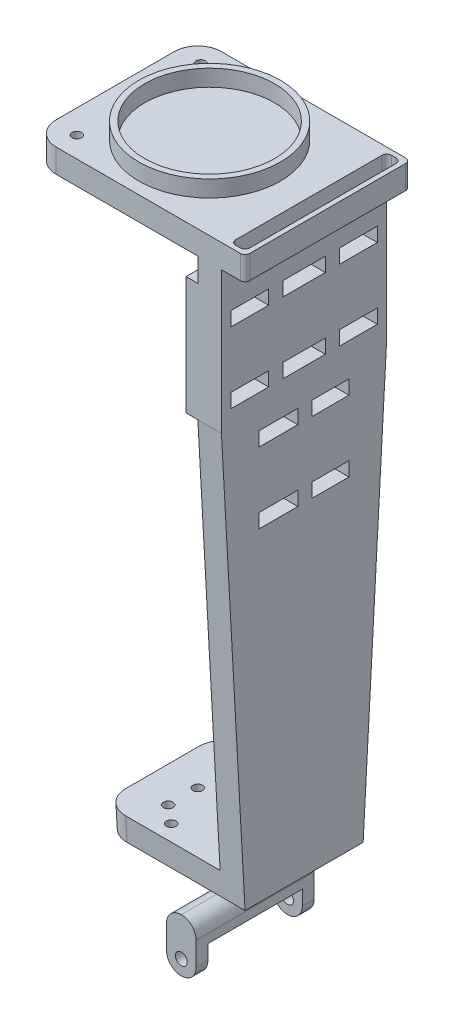
SolidWorks part; units mm, degrees
ref_plane "Front Plane" through (0, 0, 0) normal (0, 0, 1) x (1, 0, 0)
ref_plane "Top Plane" through (0, 0, 0) normal (0, 1, 0) x (1, 0, 0)
ref_plane "Right Plane" through (0, 0, 0) normal (1, 0, 0) x (0, 0, -1)
sketch "Sketch1" plane through (0, 0, 0) normal (0, 1, 0) x (1, 0, 0)
  line L1 (0, 0) -> (-80, 0)
  line L2 (0, 0) -> (0, -70)
  line L3 (0, -70) -> (-80, -70)
  line L4 (-80, 0) -> (-80, -70)
  dimension "D1" = 80
  dimension "D2" = 70
extrude "Boss-Extrude1" add sketch "Sketch1" along normal blind 10
sketch "Sketch2" plane through (0, 0, 0) normal (0, -1, 0) x (1, 0, 0)
  line L0 (0, 0) -> (-80, 0) construction
  line L1 (0, 70) -> (-10, 70)
  line L2 (0, 70) -> (0, 0)
  line L3 (0, 0) -> (-10, 0)
  line L4 (-10, 70) -> (-10, 0)
  dimension "D1" = 10
extrude "Boss-Extrude2" add sketch "Sketch2" along normal blind 450
sketch "Sketch3" plane through (0, 10, 0) normal (0, 1, 0) x (1, 0, 0)
  line L0 (0, 0) -> (-80, -70) construction
  line L1 (-80, -70) -> (-80, 0) construction
  line L2 (-80, 0) -> (0, -70) construction
  line L3 (0, -70) -> (0, 0) construction
  line L4 (0, 0) -> (-80, 0) construction
  line L5 (-80, 0) -> (-80, -70) construction
  line L6 (-80, -70) -> (0, -70) construction
  circle A0 centre (-40, -35) radius 27.5
  circle A1 centre (-40, -35) radius 30
  dimension "D1" = 55
  dimension "D2" = 60
extrude "Boss-Extrude3" add sketch "Sketch3" along normal blind 7
sketch "Sketch6" plane through (0, 10, 0) normal (0, 1, 0) x (1, 0, 0)
  line L0 (-80, -70) -> (-80, -35) construction
  line L1 (-80, 0) -> (-80, -70) construction
  line L2 (-80, -35) -> (-40, -70) construction
  line L3 (-80, -70) -> (0, -70) construction
  line L4 (-40, -70) -> (-80, -70) construction
  line L5 (-80, -70) -> (-80, -35) construction
  line L6 (-80, -35) -> (-80, 0) construction
  line L7 (-80, 0) -> (-40, 0) construction
  line L8 (0, 0) -> (-80, 0) construction
  line L9 (-40, 0) -> (-80, -35) construction
  line L10 (-80, -52.5) -> (-60, -70) construction
  line L11 (-80, -17.5) -> (-60, 0) construction
  circle A0 centre (-70, -61.25) radius 2
  circle A1 centre (-70, -8.75) radius 2
  dimension "D1" = 4
  dimension "D2" = 4
extrude "Cut-Extrude3" cut sketch "Sketch6" against normal blind 27
sketch "Sketch7" plane through (-10, 0, 0) normal (-1, 0, 0) x (0, 0, 1)
  line L0 (70, -450) -> (70, 0) construction
  line L1 (0, -450) -> (70, -450)
  line L2 (0, -450) -> (0, -240)
  line L3 (0, -240) -> (70, -240)
  line L4 (70, -450) -> (70, -240)
  dimension "D1" = 210
extrude "Cut-Extrude4" cut sketch "Sketch7" against normal blind 27
sketch "Sketch10" plane through (-10, 0, 0) normal (-1, 0, 0) x (0, 0, 1)
  line L0 (0, 0) -> (0, -120) construction
  line L1 (0, -240) -> (0, 0) construction
  line L2 (0, -120) -> (70, -120) construction
  line L3 (70, -240) -> (70, 0) construction
  line L4 (70, -120) -> (70, 0) construction
  line L5 (70, 0) -> (0, 0) construction
  line L6 (0, 0) -> (70, -120) construction
  line L7 (70, 0) -> (0, -120) construction
  line L8 (0, -240) -> (70, -240) construction
  line L9 (70, -240) -> (35, -240) construction
  line L10 (35, -240) -> (0, -240) construction
  line L11 (0, -60) -> (10, -240)
  line L12 (0, -240) -> (0, -60)
  line L13 (70, -60) -> (60, -240)
  line L14 (60, -240) -> (70, -240)
  line L15 (70, -240) -> (70, -60)
  line L16 (0, -240) -> (10, -240)
  dimension "D1" = 10
  dimension "D2" = 10
extrude "Cut-Extrude5" cut sketch "Sketch10" against normal blind 70
sketch "Sketch11" plane through (-10, 0, 0) normal (-1, 0, 0) x (0, 0, 1)
  line L0 (10.1166, -240) -> (60, -240)
  line L1 (60, -240) -> (10, -240) construction
  line L2 (60, -240) -> (60.5556, -230)
  line L3 (70, -60) -> (60, -240) construction
  line L4 (60.5556, -230) -> (9.4444, -230)
  line L5 (10, -240) -> (0, -60) construction
  line L6 (9.4444, -230) -> (10.1166, -240)
  dimension "D1" = 10
extrude "Boss-Extrude5" add sketch "Sketch11" along normal blind 50
sketch "Sketch12" plane through (0, -240, 0) normal (0, -1, 0) x (1, 0, 0)
  line L0 (-60, 60) -> (0, 10) construction
  line L1 (0, 10) -> (0, 60) construction
  line L2 (0, 60) -> (-60, 10.1166) construction
  circle A0 centre (-30, 35) radius 7.5
  circle A1 centre (-30, 35) radius 10
  circle A2 centre (-30, 35) radius 2.5
  dimension "D1" = 15
  dimension "D2" = 20
  dimension "D3" = 5
extrude "Boss-Extrude6" add sketch "Sketch12" along normal blind 25 contours A2 | A1 A0 region at (-39.7172, -240, 35) region at (-30, -240, 35)
sketch "Sketch13" plane through (0, -240, 0) normal (0, -1, 0) x (-1, 0, 0)
  line L0 (60, -60) -> (0, -60) construction
  line L1 (0, -60) -> (0, -10) construction
  line L2 (0, -10) -> (60, -10.1166) construction
  line L3 (60, -10.1166) -> (60, -60) construction
  line L4 (60, -60) -> (30, -60) construction
  line L5 (30, -60) -> (0, -60) construction
  line L6 (0, -60) -> (0, -35) construction
  line L7 (0, -35) -> (0, -10) construction
  line L8 (0, -10) -> (30, -10.0583) construction
  line L9 (30, -10.0583) -> (60, -10.1166) construction
  line L10 (60, -10.1166) -> (60, -35.0583) construction
  line L11 (60, -35.0583) -> (60, -60) construction
  line L12 (60, -35.0583) -> (30, -60) construction
  line L13 (30, -60) -> (0, -35) construction
  line L14 (0, -35) -> (30, -10.0583) construction
  line L15 (30, -10.0583) -> (60, -35.0583) construction
  line L16 (45, -47.5291) -> (45, -60) construction
  line L17 (45, -60) -> (45, -10.0874) construction
  line L18 (45, -47.5291) -> (15, -47.5) construction
  line L19 (15, -47.5) -> (15, -22.5291) construction
  line L20 (15, -22.5291) -> (45, -22.5583) construction
  line L21 (45, -47.5291) -> (30, -60) construction
  line L22 (30, -60) -> (45, -47.5291) construction
  line L23 (45, -47.5291) -> (37.5, -53.7646) construction
  line L24 (37.5, -53.7646) -> (37.5, -16.3083) construction
  circle A0 centre (45, -47.5291) radius 2
  circle A1 centre (45, -22.5583) radius 2
  circle A2 centre (45, -35.0437) radius 2
  circle A3 centre (37.5, -53.7646) radius 2
  circle A4 centre (37.5, -16.3083) radius 2
  dimension "D1" = 4
  dimension "D2" = 4
  dimension "D3" = 4
  dimension "D4" = 4
  dimension "D5" = 4
extrude "Cut-Extrude6" cut sketch "Sketch13" against normal blind 25
sketch "Sketch14" plane through (-10, 0, 0) normal (-1, 0, 0) x (0, 0, 1)
  line L1 (0, -60) -> (24, -60)
  line L2 (0, -60) -> (0, -10)
  line L3 (0, -10) -> (24, -10)
  line L4 (24, -60) -> (24, -10)
  line L5 (2, -12) -> (22, -12)
  line L6 (2, -12) -> (2, -58)
  line L7 (2, -58) -> (22, -58)
  line L8 (22, -12) -> (22, -58)
  dimension "D1" = 50
  dimension "D2" = 24
  dimension "D3" = 2
  dimension "D4" = 2
  dimension "D5" = 2
  dimension "D6" = 2
extrude "Boss-Extrude7" add sketch "Sketch14" along normal blind 5
sketch "Sketch15" plane through (-10, 0, 0) normal (-1, 0, 0) x (0, 0, 1)
  line L1 (70, -60) -> (46, -60)
  line L2 (70, -60) -> (70, -10)
  line L3 (70, -10) -> (46, -10)
  line L4 (46, -60) -> (46, -10)
  line L5 (68, -58) -> (48, -58)
  line L6 (68, -58) -> (68, -12)
  line L7 (68, -12) -> (48, -12)
  line L8 (48, -58) -> (48, -12)
  dimension "D1" = 50
  dimension "D2" = 24
  dimension "D3" = 2
  dimension "D4" = 2
  dimension "D5" = 2
  dimension "D6" = 2
extrude "Boss-Extrude8" add sketch "Sketch15" along normal blind 5
sketch "Sketch16" plane through (-10, 0, 0) normal (-1, 0, 0) x (0, 0, 1)
  line L1 (24, -10) -> (46, -10)
  line L2 (24, -10) -> (24, -60)
  line L3 (24, -60) -> (46, -60)
  line L4 (46, -10) -> (46, -60)
  line L5 (24, -12) -> (46, -12)
  line L6 (24, -12) -> (24, -58)
  line L7 (24, -58) -> (46, -58)
  line L8 (46, -12) -> (46, -58)
  line M6 (24, -10) -> (24, -60)
  line M12 (46, -60) -> (46, -10)
  dimension "D1" = 2
  dimension "D2" = 2
extrude "Boss-Extrude9" add sketch "Sketch16" along normal blind 5 contours L5 L4 L1 M6 | L7 L3 M6 M12 region at (-10, -11, 35) region at (-10, -59, 35)
sketch "Sketch17" plane through (-10, 0, 0) normal (-1, 0, 0) x (0, 0, 1)
  line L0 (0, -60) -> (70, -60) construction
  line L1 (70, -60) -> (35, -60) construction
  line L2 (35, -60) -> (0, -60) construction
  line L3 (12, -12) -> (12, -60) construction
  line L4 (22, -12) -> (2, -12) construction
  line L5 (58, -12) -> (58, -60) construction
  line L6 (68, -12) -> (48, -12) construction
  line L7 (12, -60) -> (58, -60)
  line L8 (58, -60) -> (58, -110)
  line L9 (58, -110) -> (12, -110)
  line L10 (12, -110) -> (12, -60)
  line L12 (14, -62) -> (33.659, -62)
  line L13 (14, -62) -> (14, -108)
  line L14 (14, -108) -> (33.659, -108)
  line L15 (33.659, -62) -> (33.659, -108)
  line L16 (35.659, -62) -> (56, -62)
  line L17 (35.659, -62) -> (35.659, -108)
  line L18 (35.659, -108) -> (56, -108)
  line L19 (56, -62) -> (56, -108)
  dimension "D1" = 50
  dimension "D2" = 2
  dimension "D3" = 2
  dimension "D4" = 2
  dimension "D5" = 2
  dimension "D6" = 2
  dimension "D7" = 2
  dimension "D8" = 2
extrude "Boss-Extrude10" add sketch "Sketch17" along normal blind 5
sketch "Sketch18" plane through (-10, 0, 0) normal (-1, 0, 0) x (0, 0, 1)
  line L0 (2, -12) -> (2, -58) construction
  line L1 (4, -17) -> (20, -17)
  line L2 (4, -17) -> (4, -23)
  line L3 (4, -23) -> (20, -23)
  line L4 (20, -17) -> (20, -23)
  line L5 (26, -17) -> (44, -17)
  line L6 (26, -17) -> (26, -23)
  line L7 (26, -23) -> (44, -23)
  line L8 (44, -17) -> (44, -23)
  line L9 (50, -17) -> (66, -17)
  line L10 (50, -17) -> (50, -23)
  line L11 (50, -23) -> (66, -23)
  line L12 (66, -17) -> (66, -23)
  line L13 (4, -47) -> (20, -47)
  line L14 (4, -47) -> (4, -53)
  line L15 (4, -53) -> (20, -53)
  line L16 (20, -47) -> (20, -53)
  line L17 (26, -47) -> (44, -47)
  line L18 (26, -47) -> (26, -53)
  line L19 (26, -53) -> (44, -53)
  line L20 (44, -47) -> (44, -53)
  line L21 (50, -47) -> (66, -47)
  line L22 (50, -47) -> (50, -53)
  line L23 (50, -53) -> (66, -53)
  line L24 (66, -47) -> (66, -53)
  line L25 (22, -58) -> (22, -12) construction
  line L26 (22, -12) -> (2, -12) construction
  line L27 (2, -58) -> (22, -58) construction
  line L28 (24, -58) -> (24, -12) construction
  line L29 (24, -12) -> (46, -12) construction
  line L30 (24, -58) -> (46, -58) construction
  line L31 (48, -58) -> (68, -58) construction
  line L32 (68, -12) -> (48, -12) construction
  line L33 (46, -12) -> (46, -58) construction
  line L34 (68, -58) -> (68, -12) construction
  line L35 (48, -12) -> (48, -58) construction
  point P28 (12, -12)
  dimension "D1" = 2
  dimension "D2" = 2
  dimension "D3" = 5
  dimension "D4" = 35
  dimension "D5" = 2
  dimension "D6" = 5
  dimension "D7" = 35
  dimension "D8" = 35
  dimension "D9" = 5
  dimension "D10" = 2
  dimension "D11" = 2
  dimension "D12" = 2
  dimension "D13" = 2
  dimension "D14" = 2
  dimension "D15" = 2
  dimension "D16" = 2
  dimension "D17" = 2
  dimension "D18" = 2
  dimension "D19" = 5
  dimension "D20" = 5
  dimension "D21" = 5
  dimension "D22" = 35
  dimension "D23" = 35
  dimension "D24" = 35
extrude "Cut-Extrude8" cut sketch "Sketch18" against normal blind 10
sketch "Sketch19" plane through (-10, 0, 0) normal (-1, 0, 0) x (0, 0, 1)
  line L0 (14, -62) -> (14, -108) construction
  line L1 (16, -67) -> (31.659, -67)
  line L2 (16, -67) -> (16, -73)
  line L3 (16, -73) -> (31.659, -73)
  line L4 (31.659, -67) -> (31.659, -73)
  line L5 (16, -97) -> (31.659, -97)
  line L6 (16, -97) -> (16, -103)
  line L7 (16, -103) -> (31.659, -103)
  line L8 (31.659, -97) -> (31.659, -103)
  line L9 (37.659, -67) -> (54, -67)
  line L10 (37.659, -67) -> (37.659, -73)
  line L11 (37.659, -73) -> (54, -73)
  line L12 (54, -67) -> (54, -73)
  line L13 (37.659, -97) -> (54, -97)
  line L14 (37.659, -97) -> (37.659, -103)
  line L15 (37.659, -103) -> (54, -103)
  line L16 (54, -97) -> (54, -103)
  line L17 (35.659, -62) -> (35.659, -108) construction
  line L18 (33.659, -62) -> (14, -62) construction
  line L19 (56, -62) -> (35.659, -62) construction
  line L20 (14, -108) -> (33.659, -108) construction
  line L21 (35.659, -108) -> (56, -108) construction
  line L22 (33.659, -108) -> (33.659, -62) construction
  line L23 (56, -108) -> (56, -62) construction
  dimension "D1" = 2
  dimension "D2" = 2
  dimension "D3" = 2
  dimension "D4" = 2
  dimension "D5" = 5
  dimension "D6" = 5
  dimension "D7" = 35
  dimension "D8" = 35
  dimension "D9" = 5
  dimension "D10" = 5
  dimension "D11" = 2
  dimension "D12" = 2
  dimension "D13" = 2
  dimension "D14" = 2
  dimension "D15" = 35
  dimension "D16" = 35
extrude "Cut-Extrude9" cut sketch "Sketch19" against normal blind 10
fillet "Fillet1" radius 10 2 edges at (-80, 5, 0) (-80, 5, 70)
fillet "Fillet2" radius 10 2 edges at (-60, -235, 60.2778) (-60, -235, 9.7805)
sketch "Sketch20" plane through (0, 0, 0) normal (1, 0, 0) x (0, 0, -1)
  line L1 (-70, 10) -> (0, 10)
  line L2 (-70, 10) -> (-70, 0)
  line L3 (-70, 0) -> (0, 0)
  line L4 (0, 10) -> (0, 0)
extrude "Boss-Extrude11" add sketch "Sketch20" along normal blind 10
sketch "Sketch21" plane through (0, 0, 0) normal (0, -1, 0) x (1, 0, 0)
  line L0 (10, 70) -> (10, 0) construction
  line L1 (2, 68) -> (8, 68)
  line L2 (2, 68) -> (2, 2)
  line L3 (2, 2) -> (8, 2)
  line L4 (8, 68) -> (8, 2)
  line L5 (0, 70) -> (0, 0) construction
  line L6 (10, 70) -> (0, 70) construction
  line L7 (10, 0) -> (0, 0) construction
  dimension "D1" = 2
  dimension "D2" = 2
  dimension "D3" = 2
  dimension "D4" = 2
extrude "Cut-Extrude10" cut sketch "Sketch21" against normal blind 10
fillet "Fillet3" radius 2 2 edges at (10, 5, 70) (10, 5, 0)
fillet "Fillet4" radius 2 2 edges at (8, 5, 2) (8, 5, 68)
fillet "Fillet5" radius 2 2 edges at (2, 5, 2) (2, 5, 68)
sketch "Sketch23" plane through (0, -240, 0) normal (0, -1, 0) x (1, 0, 0)
  line L1 (-41.5076, 24.2648) -> (-16.34, 24.2648)
  line L2 (-41.5076, 24.2648) -> (-41.5076, 49.9927)
  line L3 (-41.5076, 49.9927) -> (-16.34, 49.9927)
  line L4 (-16.34, 24.2648) -> (-16.34, 49.9927)
extrude "Cut-Extrude12" cut sketch "Sketch23" along normal blind 116
sketch "Sketch25" plane through (0, -240, 0) normal (0, -1, 0) x (-1, 0, 0)
  line L0 (0, -10) -> (0, -60) construction
  circle A0 centre (26.9951, -35) radius 6.25
  dimension "D1" = 12.5
extrude "Boss-Extrude12" add sketch "Sketch25" along normal blind 15
sketch "Sketch26" plane through (0, -255, 0) normal (0, -1, 0) x (-1, 0, 0)
  line L0 (33.2451, -35) -> (20.7451, -35) construction
  line L2 (20.7451, -10) -> (33.2451, -10)
  line L3 (20.7451, -10) -> (20.7451, -60)
  line L4 (20.7451, -60) -> (33.2451, -60)
  line L5 (33.2451, -10) -> (33.2451, -60)
  line L6 (20.7451, -10) -> (33.2451, -60) construction
  line L7 (20.7451, -60) -> (33.2451, -10) construction
  line L8 (33.2451, -10) -> (20.7451, -10)
  line L9 (33.2451, -10) -> (33.2451, -14)
  line L10 (33.2451, -14) -> (20.7451, -14)
  line L11 (20.7451, -10) -> (20.7451, -14)
  line L12 (33.2451, -60) -> (20.7451, -60)
  line L13 (33.2451, -60) -> (33.2451, -56)
  line L14 (33.2451, -56) -> (20.7451, -56)
  line L15 (20.7451, -60) -> (20.7451, -56)
  circle A0 centre (26.9951, -35) radius 6.25 construction
  point P5 (26.9951, -35)
  dimension "D1" = 50
  dimension "D2" = 4
  dimension "D3" = 4
extrude "Boss-Extrude13" add sketch "Sketch26" along normal blind 10 contours L10 L5 L2 L3 | L14 L5 L0 L3 | L5 L10 L3 L0 | L0 | L5 L14 L3 L4 region at (-26.9951, -255, 45.5) region at (-26.9951, -255, 24.5) region at (-26.9951, -255, 12) region at (-26.9951, -255, 58)
sketch "Sketch27" plane through (0, -265, 0) normal (0, -1, 0) x (1, 0, 0)
  line L0 (-20.7451, 10) -> (-20.7451, 60) construction
  line L1 (-33.2451, 10) -> (-20.7451, 10)
  line L2 (-33.2451, 10) -> (-33.2451, 15)
  line L3 (-33.2451, 15) -> (-20.7451, 15)
  line L4 (-20.7451, 10) -> (-20.7451, 15)
  line L6 (-33.2451, 60) -> (-20.7451, 60)
  line L7 (-33.2451, 60) -> (-33.2451, 55)
  line L8 (-33.2451, 55) -> (-20.7451, 55)
  line L9 (-20.7451, 60) -> (-20.7451, 55)
  dimension "D1" = 5
  dimension "D2" = 5
extrude "Boss-Extrude15" add sketch "Sketch27" along normal blind 12.5
fillet "Fillet8" radius 6.25 4 edges at (-20.7451, -277.5, 57.5) (-33.2451, -277.5, 57.5) (-20.7451, -277.5, 12.5) (-33.2451, -277.5, 12.5)
sketch "Sketch29" plane through (0, 0, 55) normal (0, 0, -1) x (-1, 0, 0)
  line L0 (26.9951, -277.5) -> (26.9951, -265) construction
  line L1 (33.2451, -265) -> (20.7451, -265) construction
  circle A0 centre (26.9951, -271.25) radius 2.5
  dimension "D1" = 5
extrude "Cut-Extrude14" cut sketch "Sketch29" against normal blind 12.5 and the other way blind 52.5
fillet "Fillet9" radius 6.25 4 edges at (-20.7451, -255, 47.5) (-33.2451, -255, 47.5) (-20.7451, -255, 22.5) (-33.2451, -255, 22.5)
sketch "Sketch30" plane through (-10, 0, 0) normal (-1, 0, 0) x (0, 0, 1)
  line L0 (24, -58) -> (46, -58) construction
  line L1 (46, -12) -> (45, -12)
  line L2 (46, -12) -> (46, -58)
  line L3 (46, -58) -> (45, -58)
  line L4 (45, -12) -> (45, -58)
  line L6 (24, -12) -> (25, -12)
  line L7 (24, -12) -> (24, -58)
  line L8 (24, -58) -> (25, -58)
  line L9 (25, -12) -> (25, -58)
  dimension "D1" = 1
  dimension "D2" = 1
extrude "Boss-Extrude16" add sketch "Sketch30" along normal blind 5
